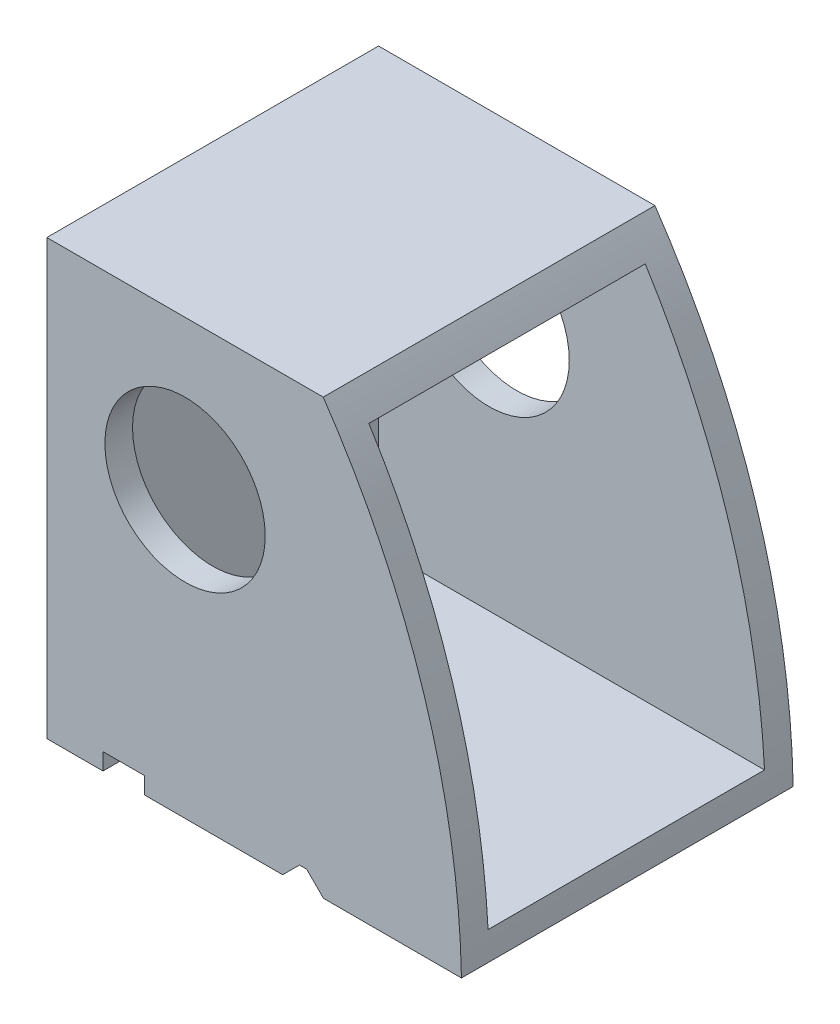
SolidWorks part; units mm, degrees
ref_plane "Front Plane" through (0, 0, 0) normal (0, 0, 1) x (1, 0, 0)
ref_plane "Top Plane" through (0, 0, 0) normal (0, 1, 0) x (1, 0, 0)
ref_plane "Right Plane" through (0, 0, 0) normal (1, 0, 0) x (0, 0, -1)
sketch "Sketch1" plane through (0, 0, 0) normal (0, 0, 1) x (1, 0, 0)
  line L1 (-10.0968, 144.4107) -> (89.9032, 144.4107)
  line L2 (-10.0968, 144.4107) -> (-10.0968, -12.5893)
  line L3 (-10.0968, -12.5893) -> (139.9032, -12.5893)
  arc A0 (89.9032, 144.4107) -> (139.9032, -12.5893) centre (-149.0036, -18.1361) cw
  dimension "D1" = 157
  dimension "D2" = 150
  dimension "D3" = 100
extrude "Boss-Extrude1" add sketch "Sketch1" along normal blind 120
shell "Shell1" thickness 10 removed face at (120.617, 67.7304, 60)
sketch "Sketch2" plane through (0, 0, 120) normal (0, 0, 1) x (1, 0, 0)
  line L0 (89.9032, 144.4107) -> (-10.0968, 144.4107) construction
  line L1 (-10.0968, 144.4107) -> (-10.0968, -12.5893) construction
  circle A0 centre (39.9032, 90.4107) radius 29
  dimension "D1" = 54
  dimension "D2" = 50
extrude "Cut-Extrude1" cut sketch "Sketch2" against normal blind 200
sketch "Sketch3" plane through (0, 0, 120) normal (0, 0, 1) x (1, 0, 0)
  line L1 (-10.0968, -12.5893) -> (139.9032, -12.5893) construction
  line L5 (75.2155, -12.5893) -> (81.3007, -6.5041)
  line L6 (81.3007, -6.5041) -> (83.9032, -6.5041)
  line L7 (83.9032, -6.5041) -> (89.9884, -12.5893)
  line L8 (89.9884, -12.5893) -> (75.2155, -12.5893)
  line L10 (25.2155, -12.5893) -> (10.2155, -12.5893)
  line L11 (25.2155, -12.5893) -> (25.2155, -6.5041)
  line L12 (25.2155, -6.5041) -> (10.2155, -6.5041)
  line L13 (10.2155, -12.5893) -> (10.2155, -6.5041)
  dimension "D1" = 56
  dimension "D2" = 15
  dimension "D3" = 50
  dimension "D4" = 135
  dimension "D5" = 135
extrude "Cut-Extrude2" cut sketch "Sketch3" against normal blind 200
